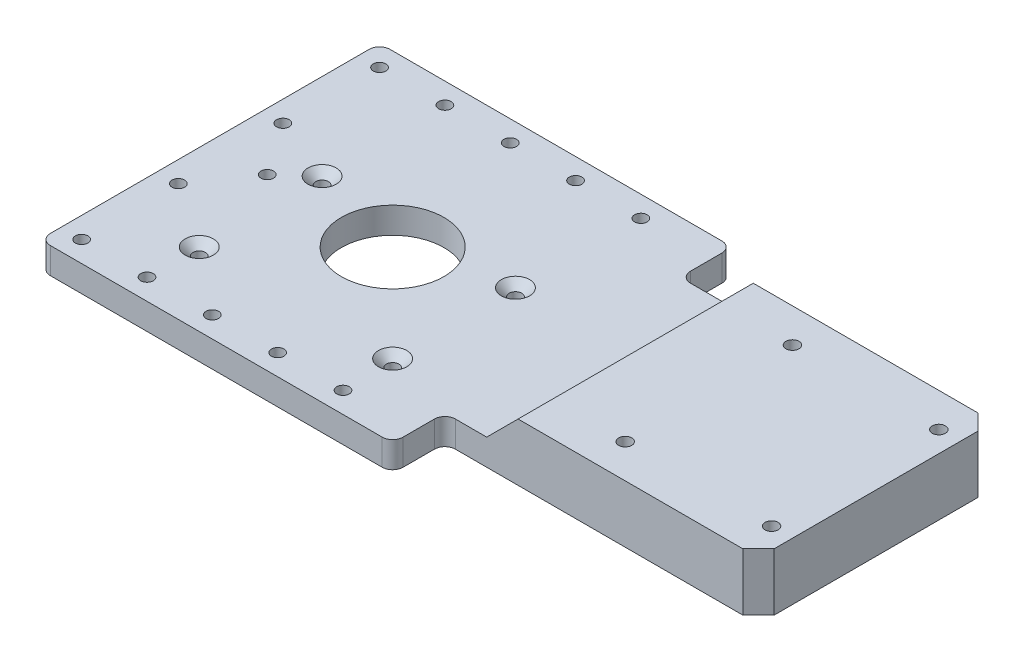
SolidWorks part; units mm, degrees
material "7075-T6, Plate (SS)"
ref_plane "Front Plane" through (0, 0, 0) normal (0, 0, 1) x (1, 0, 0)
ref_plane "Top Plane" through (0, 0, 0) normal (0, 1, 0) x (1, 0, 0)
ref_plane "Right Plane" through (0, 0, 0) normal (1, 0, 0) x (0, 0, -1)
sketch "Sketch1" plane through (0, 0, 0) normal (0, 1, 0) x (1, 0, 0)
  line L1 (0, -22.5) -> (115, -22.5)
  line L2 (0, -22.5) -> (0, 22.5)
  line L3 (0, 22.5) -> (115, 22.5)
  line L4 (115, -22.5) -> (115, 22.5)
  dimension "D1" = 45
  dimension "D2" = 115
extrude "Boss-Extrude1" add sketch "Sketch1" along normal blind 5 contours L2 L3 L4 L1
sketch "Sketch2" plane through (0, 5, 0) normal (0, 1, 0) x (1, 0, 0)
  line L0 (0, -22.5) -> (0, 22.5) construction
  circle A0 centre (22.5, 0) radius 9.8171
  dimension "D2" = 19.6342
  dimension "D1" = 22.5
extrude "Cut-Extrude1" cut sketch "Sketch2" against normal up to next
cosmetic thread "Cosmetic Thread1" parameters "D2"=20.32
hole_wizard "CSK for M2 Countersunk Flat Head Screw1" positions "Sketch3" profile "Sketch4" countersink size "M2" standard "DIN" end condition through all
sketch "Sketch3" plane through (0, 5, 0) normal (0, 1, 0) x (1, 0, 0)
  line L2 (0, -22.5) -> (115, -22.5) construction
  point P6 (4, -18.5)
  point P48 (41, -18.5)
  point P50 (41, 5)
  point P52 (4, 5)
  dimension "D3" = 4
  dimension "D5" = 37
  dimension "D6" = 27.5
sketch "Sketch4" plane through (4, 5, 18.5) normal (1, 0, 0) x (0, 0, 1)
  line L0 (0, 0) -> (0, 5)
  line L1 (0, 5) -> (1.2, 5)
  line L2 (1.2, 5) -> (1.2, 1.5)
  line L3 (1.2, 1.5) -> (2.7, 0)
  line L5 (2.7, 0) -> (0, 0)
  line L6 (-1.2, 1.5) -> (-2.7, 0) construction
  line L11 (0, -6.35) -> (0, 107.95) construction
  dimension "Thru Hole Dia." = 2.4
  dimension "Thru Hole Depth" = 5
  dimension "Near C'Sink Dia." = 5.4
  dimension "Near C'Sink Angle" = 90
sketch "Sketch13" plane through (0, 5, 0) normal (0, 1, 0) x (1, 0, 0)
  line L0 (0, -22.5) -> (115, -22.5) construction
  line L1 (115, 22.5) -> (63, 22.5)
  line L2 (115, 22.5) -> (115, -22.5)
  line L3 (115, -22.5) -> (63, -22.5)
  line L4 (63, 22.5) -> (63, -22.5)
  dimension "D1" = 52
extrude "Boss-Extrude4" add sketch "Sketch13" along normal blind 6
chamfer "Chamfer2" distance 6 angle 45 1 edges at (63, 11, 0)
hole_wizard "M3 Tapped Hole1" positions "Sketch5" profile "Sketch6" tap size "M3" standard "DIN" end condition through all
sketch "Sketch5" plane through (0, 11, 0) normal (0, 1, 0) x (1, 0, 0)
  line L1 (83, 16) -> (111, 16) construction
  line L2 (83, 16) -> (83, -16) construction
  line L3 (83, -16) -> (111, -16) construction
  line L4 (111, 16) -> (111, -16) construction
  circle A0 centre (22.5, 0) radius 9.8171 construction
  point P0 (83, 16)
  point P2 (111, 16)
  point P4 (83, -16)
  point P6 (111, -16)
  point P74 (83, 0)
  point P76 (97, 16)
  dimension "D1" = 74.5
  dimension "D2" = 28
  dimension "D3" = 32
sketch "Sketch6" plane through (83, 11, -16) normal (1, 0, 0) x (0, 0, 1)
  line L0 (0, 0) -> (0, 11)
  line L1 (0, 11) -> (1.25, 11)
  line L2 (1.25, 11) -> (1.25, 0)
  line L5 (1.25, 0) -> (0, 0)
  line L11 (0, -6.35) -> (0, 107.95) construction
  dimension "Thru Tap Drill Dia." = 2.5
  dimension "Thru Tap Drill Depth" = 11
cosmetic thread "Hole Thread7" parameters "D2"=3
cosmetic thread "Hole Thread8" parameters "D2"=3
cosmetic thread "Hole Thread9" parameters "D2"=3
cosmetic thread "Hole Thread10" parameters "D2"=3
chamfer "Chamfer1" distance 3 angle 45 2 edges at (115, 5.5, -22.5) (115, 5.5, 22.5)
sketch "Sketch14" plane through (0, 0, 0) normal (0, 1, 0) x (1, 0, 0)
  line L0 (0, 15) -> (0, -15)
  line L1 (0, -22.5) -> (0, 22.5) construction
  line L2 (0, -15) -> (-12.5, -15)
  line L3 (-12.5, -15) -> (-12.5, 15)
  line L4 (-12.5, 15) -> (0, 15)
  dimension "D1" = 12.5
  dimension "D2" = 30
extrude "Boss-Extrude5" add sketch "Sketch14" along normal up to surface (5 mm away) up to face at (31.5, 5, 0)
sketch "Sketch17" plane through (0, 0, 0) normal (0, 1, 0) x (1, 0, 0)
  line L0 (-12.5, 15) -> (-12.5, 32.5)
  line L1 (-12.5, 32.5) -> (55, 32.5)
  line L2 (55, 32.5) -> (55, 22.5)
  line L3 (0, 22.5) -> (63, 22.5) construction
  line L4 (55, 22.5) -> (0, 22.5)
  line L5 (0, 22.5) -> (0, 15)
  line L6 (0, 15) -> (-12.5, 15)
  line L7 (-12.5, -15) -> (-12.5, -32.5)
  line L8 (-12.5, -32.5) -> (55, -32.5)
  line L9 (55, -32.5) -> (55, -22.5)
  line L10 (0, -22.5) -> (63, -22.5) construction
  line L11 (55, -22.5) -> (0, -22.5)
  line L12 (0, -22.5) -> (0, -15)
  line L13 (0, -15) -> (-12.5, -15)
  circle A0 centre (22.5, 0) radius 9.8171 construction
  dimension "D1" = 32.5
  dimension "D2" = 10
extrude "Boss-Extrude6" add sketch "Sketch17" along normal up to surface (5 mm away) up to face at (12.625, 5, 0)
fillet "Fillet1" radius 2 6 edges at (55, 2.5, 22.5) (55, 2.5, -22.5) (55, 2.5, 32.5) (55, 2.5, -32.5) (-12.5, 2.5, 32.5) (-12.5, 2.5, -32.5)
hole_wizard "CSK for M2 Countersunk Flat Head Screw2" positions "Sketch15" profile "Sketch16" countersink size "M2" standard "DIN"
sketch "Sketch15" plane through (0, 0, 0) normal (0, -1, 0) x (-1, 0, 0)
  line L1 (12.5, 30.5) -> (12.5, -30.5) construction
  line L2 (12.5, 30.5) -> (12.5, -30.5) construction
  line L3 (-53, 32.5) -> (10.5, 32.5) construction
  line L4 (10.5, -32.5) -> (-53, -32.5) construction
  point P0 (1.5, 0)
  point P2 (8.5, -10)
  point P4 (8.5, 10)
  point P17 (8.5, -28.5)
  point P19 (-4, -28.5)
  point P21 (-16.5, -28.5)
  point P23 (-41.5, -28.5)
  point P25 (-41.5, 28.5)
  point P27 (-29, 28.5)
  point P29 (-16.5, 28.5)
  point P31 (-4, 28.5)
  point P33 (8.5, 28.5)
  point P35 (-29, -28.5)
  dimension "D1" = 11
  dimension "D2" = 4
  dimension "D3" = 10
  dimension "D4" = 10
  dimension "D5" = 4
  dimension "D6" = 4
  dimension "D7" = 12.5
  dimension "D8" = 12.5
  dimension "D9" = 12.5
  dimension "D10" = 12.5
sketch "Sketch16" plane through (-1.5, 0, 0) normal (1, 0, 0) x (0, 0, -1)
  line L0 (0, 0) -> (0, 5.721)
  line L1 (0, 5.721) -> (1.2, 5)
  line L2 (1.2, 5) -> (1.2, 1.5)
  line L3 (1.2, 1.5) -> (2.7, 0)
  line L5 (2.7, 0) -> (0, 0)
  line L6 (-1.2, 1.5) -> (-2.7, 0) construction
  line L10 (0, 5.721) -> (-1.2, 5) construction
  line L11 (0, -6.35) -> (0, 107.95) construction
  dimension "Hole Dia." = 2.4
  dimension "Hole Depth" = 5
  dimension "Near C'Sink Dia." = 5.4
  dimension "Near C'Sink Angle" = 90
  dimension "Drill Angle" = 118
